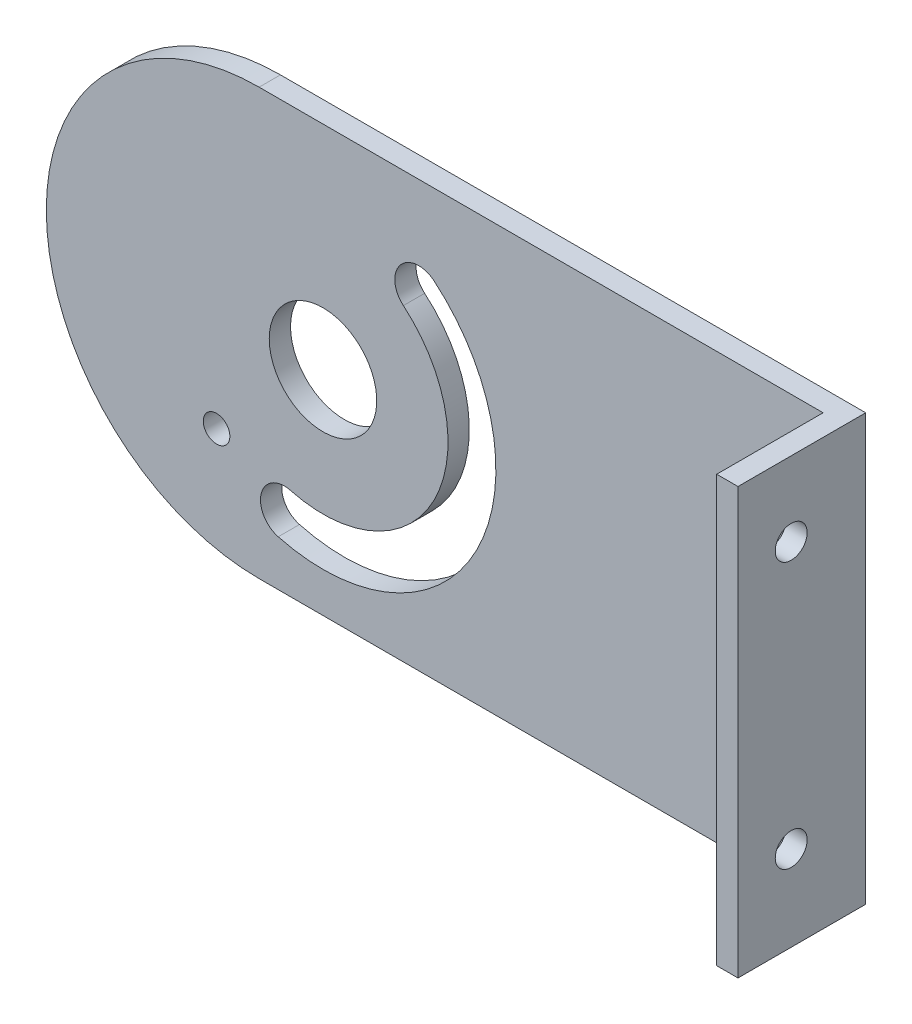
SolidWorks part; units mm, degrees
ref_plane "前视基准面" through (0, 0, 0) normal (0, 0, 1) x (1, 0, 0)
ref_plane "上视基准面" through (0, 0, 0) normal (0, 1, 0) x (1, 0, 0)
ref_plane "右视基准面" through (0, 0, 0) normal (1, 0, 0) x (0, 0, -1)
other "Configuration Table"
sketch "草图2" plane through (0, 0, 0) normal (0, 0, 1) x (1, 0, 0)
  line L0 (0, 0) -> (0, 40)
  line L1 (0, 40) -> (75, 40)
  line L2 (75, 40) -> (75, 0)
  line L3 (75, 0) -> (0, 0)
  dimension "D1" = 40
  dimension "D2" = 75
extrude "凸台-拉伸1" add sketch "草图2" along normal blind 2
sketch "草图3" plane through (0, 0, 0) normal (0, 0, -1) x (-1, 0, 0)
  line L1 (0, 40) -> (0, 0) construction
  line L2 (-75, 0) -> (-75, 40) construction
  line L6 (-75, 40) -> (0, 40) construction
  line L7 (-26, 20) -> (-35, 30.7238) construction
  line L8 (-26, 20) -> (-22.3753, 6.4774) construction
  circle A0 centre (-26, 20) radius 5.05
  circle A1 centre (-26, 20) radius 14 construction
  arc A3 (-35, 30.7238) -> (-22.3753, 6.4774) centre (-26, 20) ccw construction
  arc A4 (-36.4464, 32.4473) -> (-21.7928, 4.3041) centre (-26, 20) ccw
  arc A5 (-33.5536, 29.0003) -> (-22.9578, 8.6506) centre (-26, 20) ccw
  arc A6 (-33.5536, 29.0003) -> (-36.4464, 32.4473) centre (-35, 30.7238) ccw
  arc A7 (-21.7928, 4.3041) -> (-22.9578, 8.6506) centre (-22.3753, 6.4774) ccw
  circle A8 centre (-16, 10.202) radius 1.25
  point P13 (-38.4176, 13.5344)
  dimension "D1" = 10.1
  dimension "D4" = 28
  dimension "D5" = 20
  dimension "D8" = 4.5
  dimension "D9" = 2.5
  dimension "D2" = 26
  dimension "D3" = 75
  dimension "D6" = 155
  dimension "D7" = 9
  dimension "D10" = 10
extrude "切除-拉伸1" cut sketch "草图3" against normal through all
fillet "圆角1" radius 20 2 edges at (0, 40, 1) (0, 0, 1)
sketch "草图7" plane through (0, 0, 0) normal (0, 0, -1) x (-1, 0, 0)
  line L0 (-75, 40) -> (-20, 40) construction
  line L1 (-75, 0) -> (-73, 0)
  line L2 (-75, 0) -> (-75, 40)
  line L3 (-75, 40) -> (-73, 40)
  line L4 (-73, 0) -> (-73, 40)
  dimension "D1" = 2
extrude "凸台-拉伸3" add sketch "草图7" against normal blind 12
sketch "草图8" plane through (73, 0, 0) normal (-1, 0, 0) x (0, 0, 1)
  line L0 (12, 40) -> (2, 40) construction
  line L2 (2, 0) -> (2, 40) construction
  circle A0 centre (7, 33) radius 1.5
  circle A1 centre (7, 8) radius 1.5
  dimension "D2" = 25
  dimension "D3" = 3
  dimension "D1" = 7
  dimension "D4" = 5
extrude "切除-拉伸2" cut sketch "草图8" against normal blind 10
